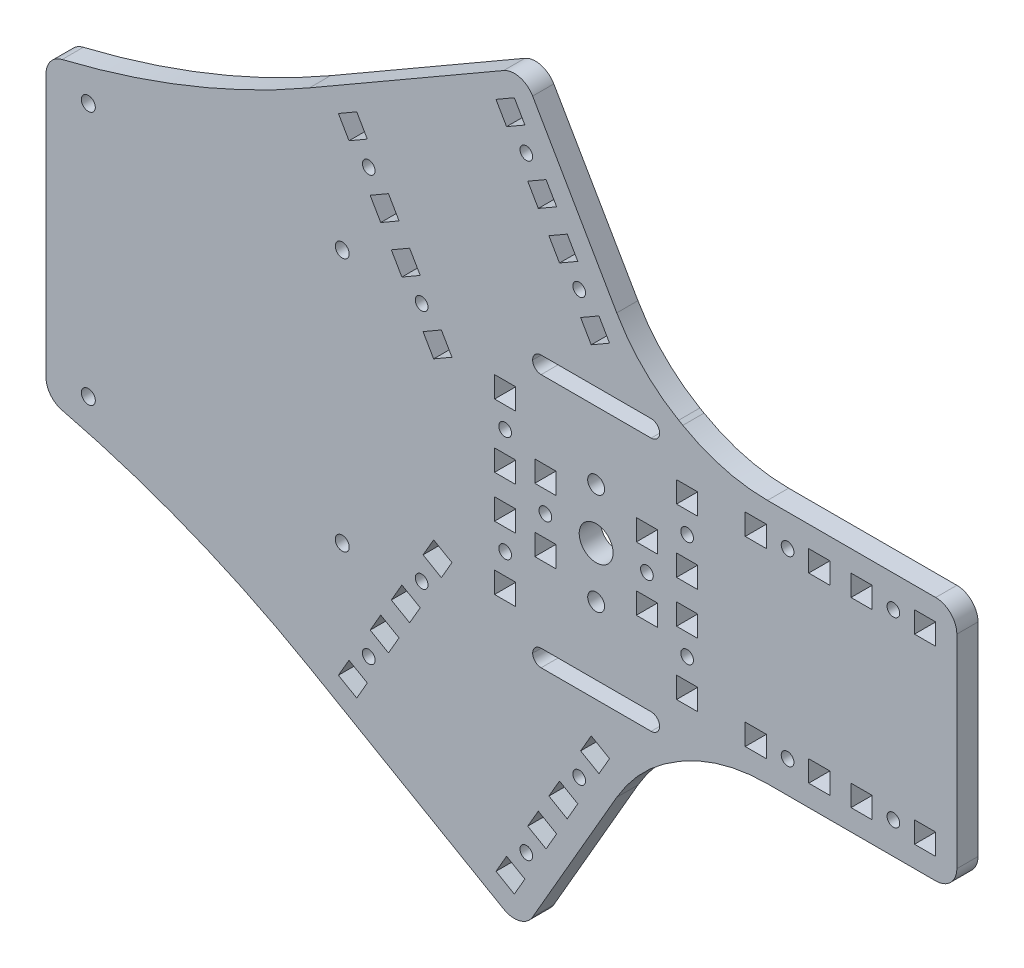
SolidWorks part; units mm, degrees
ref_plane "Plan de face" through (0, 0, 0) normal (0, 0, 1) x (1, 0, 0)
ref_plane "Plan de dessus" through (0, 0, 0) normal (0, 1, 0) x (1, 0, 0)
ref_plane "Plan de droite" through (0, 0, 0) normal (1, 0, 0) x (0, 0, -1)
sketch "Esquisse1" plane through (0, 0, 0) normal (0, 0, 1) x (1, 0, 0)
  line L0 (0, 0) -> (17.8582, 0) construction
  line L1 (-20, 40) -> (20, 40) construction
  line L2 (20, 40) -> (20, -40) construction
  line L3 (20, -40) -> (-20, -40) construction
  line L4 (-20, -40) -> (-20, 40) construction
  line L13 (0, 0) -> (0, 13.4404) construction
  line L16 (-20, -40) -> (-20, 40) construction
  line L18 (0, -40) -> (0, 40) construction
  line L19 (-15, -32) -> (-15, -28)
  line L20 (-15, 32) -> (15, 32)
  line L21 (-15, 32) -> (-15, 28)
  line L22 (-15, 28) -> (15, 28)
  line L23 (15, 32) -> (15, 28)
  line L24 (-15, -28) -> (15, -28)
  line L25 (15, -32) -> (15, -28)
  line L26 (-15, -32) -> (15, -32)
  line L32 (-60, 30) -> (-120, 30) construction
  line L42 (-15, 40) -> (15, 40) construction
  line L43 (-15, 40) -> (-15, 36) construction
  line L44 (-15, 36) -> (15, 36) construction
  line L45 (15, 40) -> (15, 36) construction
  line L46 (-15, -40) -> (-15, -36) construction
  line L47 (-15, -40) -> (15, -40) construction
  line L48 (15, -40) -> (15, -36) construction
  line L49 (-15, -36) -> (15, -36) construction
  line L55 (-130, 35) -> (-130, -35)
  line L57 (29.7705, 29) -> (85.235, 29)
  line L58 (85.235, 29) -> (85.235, -29)
  line L60 (85.235, -29) -> (29.7705, -29)
  line L62 (29.7705, -29) -> (20, -34.641)
  line L63 (29.7705, 29) -> (20, 34.641)
  line L64 (-40, -11.282) -> (-40, 0) construction
  line L65 (-67.7323, -59.3157) -> (-40, -11.282) construction
  line L66 (-17.5028, -88.3157) -> (-67.7323, -59.3157)
  line L67 (10.2295, -40.282) -> (-17.5028, -88.3157)
  line L68 (10.2295, -40.282) -> (20, -34.641)
  line L69 (10.2295, 40.282) -> (20, 34.641)
  line L70 (-17.5028, 88.3157) -> (10.2295, 40.282)
  line L71 (-67.7323, 59.3157) -> (-17.5028, 88.3157)
  line L72 (-40, 11.282) -> (-67.7323, 59.3157) construction
  line L73 (-40, 11.282) -> (-40, 0) construction
  circle A1 centre (0, 0) radius 4
  circle A2 centre (12, 0) radius 2 construction
  circle A3 centre (0, -12) radius 2
  circle A4 centre (-12, 0) radius 2 construction
  circle A5 centre (0, 12) radius 2
  circle A6 centre (-60, 30) radius 1.65
  circle A7 centre (-60, -30) radius 1.65
  circle A8 centre (-120, 30) radius 1.65
  circle A9 centre (-120, -30) radius 1.65
  arc A10 (-67.7323, 59.3157) -> (-130, 35) centre (-178.6043, 251.3517) cw
  arc A12 (-67.7323, -59.3157) -> (-130, -35) centre (-178.6043, -251.3517) ccw
  point P12 (0, 0)
  point P19 (0, 0)
  point P21 (-28.8675, -50)
  point P24 (57.735, 0)
  point P27 (-28.8675, 50)
  point P42 (0, 0)
  point P56 (0, 0)
  point P64 (0, 0)
  point P67 (0, 0)
  point P69 (-130, 46.2806)
  point P134 (0, 0)
  line B0 (50.235, 24) -> (55.235, 24)
  line B1 (50.235, 24) -> (50.235, 19)
  line B2 (50.235, 19) -> (55.235, 19)
  line B3 (55.235, 24) -> (55.235, 19)
  line B4 (40.235, 24) -> (35.235, 24)
  line B5 (40.235, 24) -> (40.235, 19)
  line B6 (40.235, 19) -> (35.235, 19)
  line B7 (35.235, 24) -> (35.235, 19)
  circle B8 centre (45.235, 21.5) radius 1.5
  line B9 (65.235, 24) -> (60.235, 24)
  line B10 (65.235, 24) -> (65.235, 19)
  line B11 (65.235, 19) -> (60.235, 19)
  line B12 (60.235, 24) -> (60.235, 19)
  line B13 (75.235, 24) -> (80.235, 24)
  line B14 (75.235, 24) -> (75.235, 19)
  line B15 (75.235, 19) -> (80.235, 19)
  line B16 (80.235, 24) -> (80.235, 19)
  circle B17 centre (70.235, 21.5) radius 1.5
  line B18 (65.235, -24) -> (60.235, -24)
  line B19 (65.235, -24) -> (65.235, -19)
  line B20 (65.235, -19) -> (60.235, -19)
  line B21 (60.235, -24) -> (60.235, -19)
  line B22 (75.235, -24) -> (80.235, -24)
  line B23 (75.235, -24) -> (75.235, -19)
  line B24 (75.235, -19) -> (80.235, -19)
  line B25 (80.235, -24) -> (80.235, -19)
  circle B26 centre (70.235, -21.5) radius 1.5
  line B27 (50.235, -24) -> (55.235, -24)
  line B28 (50.235, -24) -> (50.235, -19)
  line B29 (50.235, -19) -> (55.235, -19)
  line B30 (55.235, -24) -> (55.235, -19)
  line B31 (40.235, -24) -> (35.235, -24)
  line B32 (40.235, -24) -> (40.235, -19)
  line B33 (40.235, -19) -> (35.235, -19)
  line B34 (35.235, -24) -> (35.235, -19)
  line B35 (45.235, -21.5) -> (45.235, -27.7802) construction
  circle B36 centre (45.235, -21.5) radius 1.5
  line B37 (80.235, -24) -> (80.235, 24) construction
  line B38 (35.235, -24) -> (35.235, 24) construction
  line B39 (35.235, 0) -> (80.235, 0) construction
  line B40 (-4.3329, -55.5048) -> (-6.8329, -59.8349)
  line B41 (-4.3329, -55.5048) -> (-8.663, -53.0048)
  line B42 (-8.663, -53.0048) -> (-11.163, -57.3349)
  line B43 (-6.8329, -59.8349) -> (-11.163, -57.3349)
  line B44 (0.6671, -46.8446) -> (3.1671, -42.5144)
  line B45 (0.6671, -46.8446) -> (-3.663, -44.3446)
  line B46 (-3.663, -44.3446) -> (-1.163, -40.0144)
  line B47 (3.1671, -42.5144) -> (-1.163, -40.0144)
  circle B48 centre (-3.998, -49.9247) radius 1.5
  line B49 (-11.8329, -68.4952) -> (-9.3329, -64.1651)
  line B50 (-11.8329, -68.4952) -> (-16.163, -65.9952)
  line B51 (-16.163, -65.9952) -> (-13.663, -61.6651)
  line B52 (-9.3329, -64.1651) -> (-13.663, -61.6651)
  line B53 (-16.8329, -77.1554) -> (-19.3329, -81.4856)
  line B54 (-16.8329, -77.1554) -> (-21.163, -74.6554)
  line B55 (-21.163, -74.6554) -> (-23.663, -78.9856)
  line B56 (-19.3329, -81.4856) -> (-23.663, -78.9856)
  circle B57 centre (-16.498, -71.5753) radius 1.5
  line B58 (-53.4021, -44.4952) -> (-50.9021, -40.1651)
  line B59 (-53.4021, -44.4952) -> (-49.072, -46.9952)
  line B60 (-49.072, -46.9952) -> (-46.572, -42.6651)
  line B61 (-50.9021, -40.1651) -> (-46.572, -42.6651)
  line B62 (-58.4021, -53.1554) -> (-60.9021, -57.4856)
  line B63 (-58.4021, -53.1554) -> (-54.072, -55.6554)
  line B64 (-54.072, -55.6554) -> (-56.572, -59.9856)
  line B65 (-60.9021, -57.4856) -> (-56.572, -59.9856)
  circle B66 centre (-53.7371, -50.0753) radius 1.5
  line B67 (-45.9021, -31.5048) -> (-48.4021, -35.8349)
  line B68 (-45.9021, -31.5048) -> (-41.572, -34.0048)
  line B69 (-41.572, -34.0048) -> (-44.072, -38.3349)
  line B70 (-48.4021, -35.8349) -> (-44.072, -38.3349)
  line B71 (-40.9021, -22.8446) -> (-38.4021, -18.5144)
  line B72 (-40.9021, -22.8446) -> (-36.572, -25.3446)
  line B73 (-36.572, -25.3446) -> (-34.072, -21.0144)
  line B74 (-38.4021, -18.5144) -> (-34.072, -21.0144)
  circle B75 centre (-41.2371, -28.4247) radius 1.5
  line B76 (-17.6175, -30.5144) -> (-40.1175, -69.4856) construction
  line B77 (-45.9021, 31.5048) -> (-48.4021, 35.8349)
  line B78 (-45.9021, 31.5048) -> (-41.572, 34.0048)
  line B79 (-41.572, 34.0048) -> (-44.072, 38.3349)
  line B80 (-48.4021, 35.8349) -> (-44.072, 38.3349)
  line B81 (-40.9021, 22.8446) -> (-38.4021, 18.5144)
  line B82 (-40.9021, 22.8446) -> (-36.572, 25.3446)
  line B83 (-36.572, 25.3446) -> (-34.072, 21.0144)
  line B84 (-38.4021, 18.5144) -> (-34.072, 21.0144)
  circle B85 centre (-41.2371, 28.4247) radius 1.5
  line B86 (-53.4021, 44.4952) -> (-50.9021, 40.1651)
  line B87 (-53.4021, 44.4952) -> (-49.072, 46.9952)
  line B88 (-49.072, 46.9952) -> (-46.572, 42.6651)
  line B89 (-50.9021, 40.1651) -> (-46.572, 42.6651)
  line B90 (-58.4021, 53.1554) -> (-60.9021, 57.4856)
  line B91 (-58.4021, 53.1554) -> (-54.072, 55.6554)
  line B92 (-54.072, 55.6554) -> (-56.572, 59.9856)
  line B93 (-60.9021, 57.4856) -> (-56.572, 59.9856)
  circle B94 centre (-53.7371, 50.0753) radius 1.5
  line B95 (-11.8329, 68.4952) -> (-9.3329, 64.1651)
  line B96 (-11.8329, 68.4952) -> (-16.163, 65.9952)
  line B97 (-16.163, 65.9952) -> (-13.663, 61.6651)
  line B98 (-9.3329, 64.1651) -> (-13.663, 61.6651)
  line B99 (-16.8329, 77.1554) -> (-19.3329, 81.4856)
  line B100 (-16.8329, 77.1554) -> (-21.163, 74.6554)
  line B101 (-21.163, 74.6554) -> (-23.663, 78.9856)
  line B102 (-19.3329, 81.4856) -> (-23.663, 78.9856)
  circle B103 centre (-16.498, 71.5753) radius 1.5
  line B104 (-4.3329, 55.5048) -> (-6.8329, 59.8349)
  line B105 (-4.3329, 55.5048) -> (-8.663, 53.0048)
  line B106 (-8.663, 53.0048) -> (-11.163, 57.3349)
  line B107 (-6.8329, 59.8349) -> (-11.163, 57.3349)
  line B108 (0.6671, 46.8446) -> (3.1671, 42.5144)
  line B109 (0.6671, 46.8446) -> (-3.663, 44.3446)
  line B110 (-3.663, 44.3446) -> (-1.163, 40.0144)
  line B111 (3.1671, 42.5144) -> (-1.163, 40.0144)
  circle B112 centre (-3.998, 49.9247) radius 1.5
  line B113 (-24, -7.5) -> (-24, -2.5)
  line B114 (-24, -7.5) -> (-19, -7.5)
  line B115 (-19, -7.5) -> (-19, -2.5)
  line B116 (-24, -2.5) -> (-19, -2.5)
  line B117 (-24, -17.5) -> (-24, -22.5)
  line B118 (-24, -17.5) -> (-19, -17.5)
  line B119 (-19, -17.5) -> (-19, -22.5)
  line B120 (-24, -22.5) -> (-19, -22.5)
  circle B121 centre (-21.5, -12.5) radius 1.5
  line B122 (-24, 7.5) -> (-24, 2.5)
  line B123 (-24, 7.5) -> (-19, 7.5)
  line B124 (-19, 7.5) -> (-19, 2.5)
  line B125 (-24, 2.5) -> (-19, 2.5)
  line B126 (-24, 17.5) -> (-24, 22.5)
  line B127 (-24, 17.5) -> (-19, 17.5)
  line B128 (-19, 17.5) -> (-19, 22.5)
  line B129 (-24, 22.5) -> (-19, 22.5)
  circle B130 centre (-21.5, 12.5) radius 1.5
  line B131 (24, 7.5) -> (24, 2.5)
  line B132 (24, 7.5) -> (19, 7.5)
  line B133 (19, 7.5) -> (19, 2.5)
  line B134 (24, 2.5) -> (19, 2.5)
  line B135 (24, 17.5) -> (24, 22.5)
  line B136 (24, 17.5) -> (19, 17.5)
  line B137 (19, 17.5) -> (19, 22.5)
  line B138 (24, 22.5) -> (19, 22.5)
  circle B139 centre (21.5, 12.5) radius 1.5
  line B140 (24, -7.5) -> (24, -2.5)
  line B141 (24, -7.5) -> (19, -7.5)
  line B142 (19, -7.5) -> (19, -2.5)
  line B143 (24, -2.5) -> (19, -2.5)
  line B144 (24, -17.5) -> (24, -22.5)
  line B145 (24, -17.5) -> (19, -17.5)
  line B146 (19, -17.5) -> (19, -22.5)
  line B147 (24, -22.5) -> (19, -22.5)
  circle B148 centre (21.5, -12.5) radius 1.5
  line B149 (24, 22.5) -> (-24, 22.5) construction
  line B150 (24, -22.5) -> (-24, -22.5) construction
  line B151 (0, -22.5) -> (0, 22.5) construction
  line B152 (14.5, -5) -> (14.5, -10)
  line B153 (14.5, -5) -> (9.5, -5)
  line B154 (9.5, -5) -> (9.5, -10)
  line B155 (14.5, -10) -> (9.5, -10)
  line B156 (14.5, 5) -> (14.5, 10)
  line B157 (14.5, 5) -> (9.5, 5)
  line B158 (9.5, 5) -> (9.5, 10)
  line B159 (14.5, 10) -> (9.5, 10)
  line B160 (12, 0) -> (18.2802, 0) construction
  circle B161 centre (12, 0) radius 1.5
  line B162 (-12, -5) -> (-12, 5) construction
  line B163 (-9.5, -5) -> (-9.5, -10)
  line B164 (-9.5, -5) -> (-14.5, -5)
  line B165 (-14.5, -5) -> (-14.5, -10)
  line B166 (-9.5, -10) -> (-14.5, -10)
  line B167 (-9.5, 5) -> (-9.5, 10)
  line B168 (-9.5, 5) -> (-14.5, 5)
  line B169 (-14.5, 5) -> (-14.5, 10)
  line B170 (-9.5, 10) -> (-14.5, 10)
  line B171 (-12, 0) -> (-5.7198, 0) construction
  circle B172 centre (-12, 0) radius 1.5
  dimension "D9" = 5
  dimension "D14" = 100
  dimension "D17" = 8
  dimension "D18" = 4
  dimension "D13" = 60
  dimension "D15" = 3.3
  dimension "D23" = 10
  dimension "D24" = 70
  dimension "D4" = 3
  dimension "D5" = 5
  dimension "D6" = 5
  dimension "D7" = 5
  dimension "D8" = 20
  dimension "D10" = 5
  dimension "D11" = 4
  dimension "D12" = 40
  dimension "D3" = 3
  dimension "D16" = 28
  dimension "D19" = 12
  dimension "D22" = 60
  dimension "D21" = 60
  dimension "D20" = 4
sketch_block_instance "Bloc1-4"
sketch_block "Bloc1"
sketch_block_instance "Trou M3 plots 5mm-54"
sketch_block "Trou M3 plots 5mm" parameters "D2"=3, "D1"=5, "D3"=5, "D4"=8
sketch_block_instance "Trou M3 plots 5mm-56"
sketch_block_instance "Trou M3 plots 5mm-55"
sketch_block_instance "Trou M3 plots 5mm-52"
sketch_block_instance "Bloc1-5"
sketch_block_instance "Bloc1-6"
sketch_block_instance "Bloc1-10"
sketch_block_instance "Trou M3 plots 5mm-61"
sketch_block_instance "Trou M3 plots 5mm-62"
extrude "Boss.-Extru.1" add sketch "Esquisse1" along normal blind 5
fillet "Congé1" radius 2 8 edges at (-15, -32, 2.5) (-15, -28, 2.5) (15, -28, 2.5) (15, -32, 2.5) (15, 28, 2.5) (15, 32, 2.5) (-15, 28, 2.5) (-15, 32, 2.5)
fillet "Congé2" radius 5 6 edges at (-17.5028, -88.3157, 2.5) (85.235, -29, 2.5) (85.235, 29, 2.5) (-17.5028, 88.3157, 2.5) (-130, -35, 2.5) (-130, 35, 2.5)
fillet "Congé3" radius 40 4 edges at (10.2295, -40.282, 2.5) (29.7705, -29, 2.5) (29.7705, 29, 2.5) (10.2295, 40.282, 2.5)
